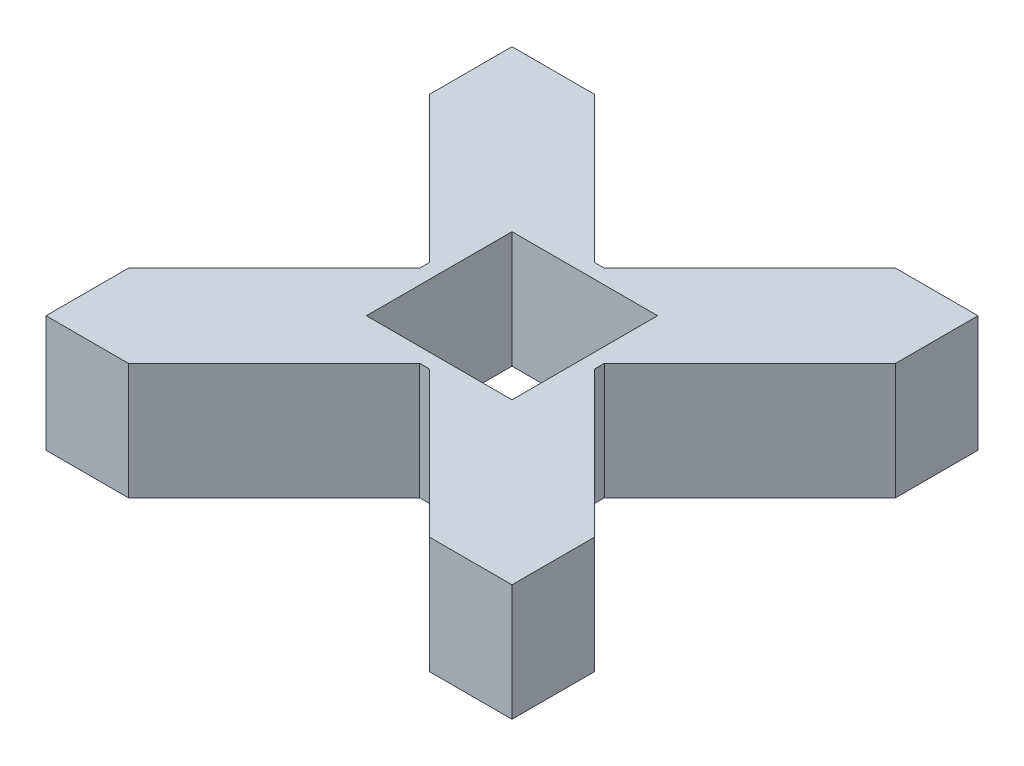
SolidWorks part; units mm, degrees
ref_plane "Front Plane" through (0, 0, 0) normal (0, 0, 1) x (1, 0, 0)
ref_plane "Top Plane" through (0, 0, 0) normal (0, 1, 0) x (1, 0, 0)
ref_plane "Right Plane" through (0, 0, 0) normal (1, 0, 0) x (0, 0, -1)
sketch "Sketch1" plane through (0, 0, 0) normal (0, 1, 0) x (1, 0, 0)
  line L0 (40, -25.8579) -> (-25.8579, 40)
  line L1 (40, -40) -> (-40, -40)
  line L2 (40, -40) -> (40, 40)
  line L3 (40, 40) -> (-40, 40)
  line L4 (-40, -40) -> (-40, 40)
  line L5 (40, -40) -> (-40, 40) construction
  line L6 (40, 40) -> (-40, -40) construction
  line L7 (25.8579, 40) -> (-40, -25.8579)
  line L8 (25.8579, -40) -> (-40, 25.8579)
  line L9 (40, 25.8579) -> (-25.8579, -40)
  line L10 (47.0711, 32.9289) -> (-32.9289, -47.0711) construction
  line L11 (32.9289, 47.0711) -> (-47.0711, -32.9289) construction
  line L12 (32.9289, -47.0711) -> (-47.0711, 32.9289) construction
  line L13 (47.0711, -32.9289) -> (-32.9289, 47.0711) construction
  line L15 (-15, 15) -> (15, 15)
  line L16 (-15, 15) -> (-15, -15)
  line L17 (-15, -15) -> (15, -15)
  line L18 (15, 15) -> (15, -15)
  line L19 (-15, 15) -> (15, -15) construction
  line L20 (-15, -15) -> (15, 15) construction
  point P0 (0, 0)
  point P22 (0, 0)
  dimension "D1" = 80
  dimension "D2" = 80
  dimension "D5" = 30
  dimension "D6" = 30
  dimension "D3" = 10
  dimension "D4" = 10
extrude "Boss-Extrude1" add sketch "Sketch1" along normal blind 20 contours L8 L7 L0 L3 L4 | L9 L2 L3 L7 L0 | L9 L0 L7 L8 | L9 L8 L7 L4 L1 | L0 L9 L8 L1 L2 | L15 L0 L7 | L18 L15 L7 L0 L9 | L15 L16 L8 L7 L0 | L8 L16 L7 | L16 L17 L9 L8 L7 | L18 L0 L9 L8 L17 | L9 L17 L8 | L18 L9 L0 region at (23.9645, 0, 23.9645) region at (9.742, 0, 9.742) region at (14.714, 0, 0) region at (23.9645, 0, -23.9645) region at (0, 0, 0) region at (9.742, 0, -9.742) region at (-9.742, 0, -9.742) region at (0, 0, -14.714) region at (-9.742, 0, 9.742) region at (0, 0, 14.714) region at (-23.9645, 0, 23.9645) region at (-23.9645, 0, -23.9645) region at (-14.714, 0, 0)
sketch "Sketch2" plane through (0, 20, 0) normal (0, 1, 0) x (1, 0, 0)
  line L1 (-12.5, 12.5) -> (12.5, 12.5)
  line L2 (-12.5, 12.5) -> (-12.5, -12.5)
  line L3 (-12.5, -12.5) -> (12.5, -12.5)
  line L4 (12.5, 12.5) -> (12.5, -12.5)
  line L5 (-12.5, 12.5) -> (12.5, -12.5) construction
  line L6 (-12.5, -12.5) -> (12.5, 12.5) construction
  point P0 (0, 0)
  dimension "D1" = 25
  dimension "D2" = 25
extrude "Cut-Extrude2" cut sketch "Sketch2" against normal through all
